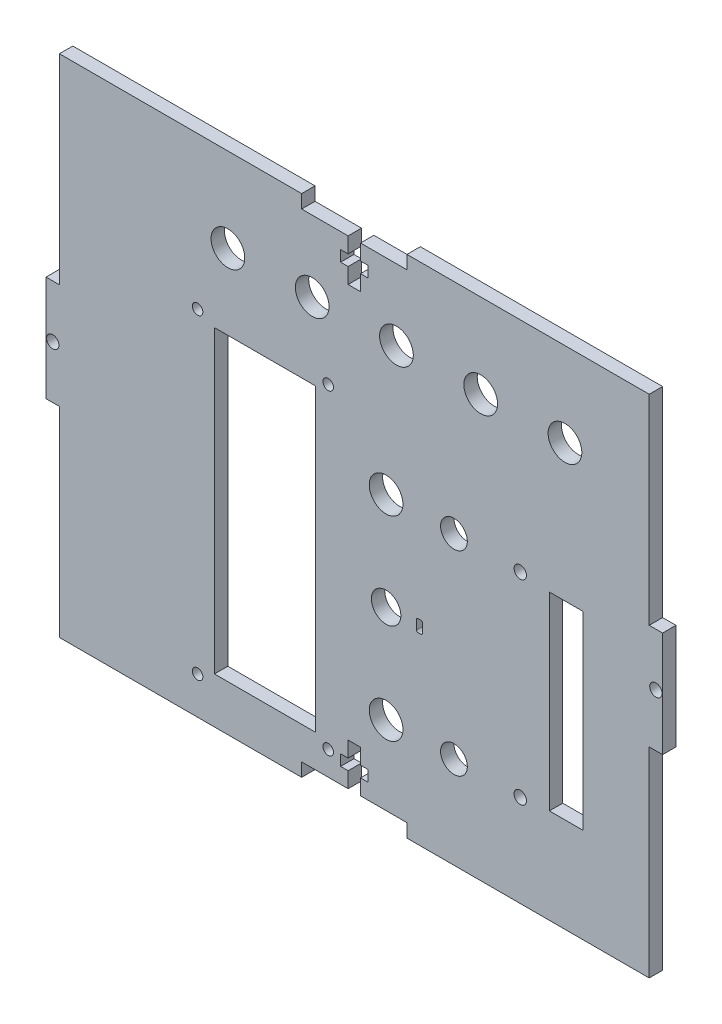
SolidWorks part; units mm, degrees
ref_plane "Front Plane" through (0, 0, 0) normal (0, 0, 1) x (1, 0, 0)
ref_plane "Top Plane" through (0, 0, 0) normal (0, 1, 0) x (1, 0, 0)
ref_plane "Right Plane" through (0, 0, 0) normal (1, 0, 0) x (0, 0, -1)
sketch "Sketch1" plane through (0, 0, 0) normal (0, 0, 1) x (1, 0, 0)
  line L0 (0, 60) -> (0, -60) construction
  line L1 (-70, 60) -> (70, 60)
  line L2 (-70, 60) -> (-70, -60)
  line L3 (-70, -60) -> (70, -60)
  line L4 (70, 60) -> (70, -60)
  line L5 (-70, 60) -> (70, -60) construction
  line L6 (-70, -60) -> (70, 60) construction
  line L7 (-70, 0) -> (70, 0) construction
  line L8 (-3.25, -50.525) -> (3.25, -50.525)
  line L9 (12.5, 60) -> (-12.5, 60)
  line L10 (12.5, 60) -> (12.5, 56.825)
  line L11 (12.5, 56.825) -> (-12.5, 56.825)
  line L12 (-12.5, 60) -> (-12.5, 56.825)
  line L13 (12.5, 60) -> (-12.5, 56.825) construction
  line L14 (12.5, 56.825) -> (-12.5, 60) construction
  line L15 (-1.47, 56.825) -> (1.47, 56.825)
  line L16 (-1.47, 56.825) -> (-1.47, 46.825)
  line L17 (-1.47, 46.825) -> (1.47, 46.825)
  line L18 (1.47, 56.825) -> (1.47, 46.825)
  line L19 (-1.47, 56.825) -> (1.47, 46.825) construction
  line L20 (-1.47, 46.825) -> (1.47, 56.825) construction
  line L21 (-3.25, 53.125) -> (3.25, 53.125)
  line L22 (-3.25, 53.125) -> (-3.25, 50.525)
  line L23 (-3.25, 50.525) -> (3.25, 50.525)
  line L24 (3.25, 53.125) -> (3.25, 50.525)
  line L25 (-3.25, 53.125) -> (3.25, 50.525) construction
  line L26 (-3.25, 50.525) -> (3.25, 53.125) construction
  line L27 (3.25, -53.125) -> (3.25, -50.525)
  line L28 (-3.25, -53.125) -> (3.25, -53.125)
  line L29 (-3.25, -53.125) -> (-3.25, -50.525)
  line L30 (-1.47, -46.825) -> (1.47, -46.825)
  line L31 (1.47, -56.825) -> (1.47, -46.825)
  line L32 (-1.47, -56.825) -> (1.47, -56.825)
  line L33 (-1.47, -56.825) -> (-1.47, -46.825)
  line L34 (12.5, -56.825) -> (-12.5, -56.825)
  line L35 (-12.5, -60) -> (-12.5, -56.825)
  line L36 (12.5, -60) -> (-12.5, -60)
  line L37 (12.5, -60) -> (12.5, -56.825)
  line L38 (73.175, -12.5) -> (70, -12.5)
  line L39 (-73.175, 12.5) -> (-70, 12.5)
  line L40 (-73.175, 12.5) -> (-73.175, -12.5)
  line L41 (-73.175, -12.5) -> (-70, -12.5)
  line L42 (-70, 12.5) -> (-70, -12.5)
  line L43 (-73.175, 12.5) -> (-70, -12.5) construction
  line L44 (-73.175, -12.5) -> (-70, 12.5) construction
  line L45 (70, 12.5) -> (70, -12.5)
  line L46 (73.175, 12.5) -> (70, 12.5)
  line L47 (73.175, 12.5) -> (73.175, -12.5)
  circle A0 centre (-71.5875, 0) radius 1.47
  circle A1 centre (71.5875, 0) radius 1.47
  point P0 (0, 0)
  point P10 (0, 58.4125)
  point P15 (0, 51.825)
  point P20 (0, 51.825)
  point P37 (-71.5875, 0)
  dimension "D11" = 2.94
  dimension "D1" = 120
  dimension "D2" = 140
  dimension "D3" = 3.175
  dimension "D4" = 10
  dimension "D5" = 2.94
  dimension "D6" = 25
  dimension "D7" = 6.5
  dimension "D8" = 2.6
  dimension "D9" = 6.3
  dimension "D10" = 3.175
extrude "Boss-Extrude1" add sketch "Sketch1" along normal mid plane 3.175 contours L21 L24 L23 L18 L17 L16 L22 L11 L12 L1 L2 L3 L4 L10 | L40 L39 L42 L41 | A0 | L38 L45 L46 L47 | A1 region at (0, 0, 0)
sketch "Sketch3" plane through (0, 0, -1.5875) normal (0, 0, -1) x (-1, 0, 0)
  line L0 (-9.6476, 0) -> (-9.6476, -15) construction
  line L5 (-9.6476, -15) -> (-19.2951, -15) construction
  line L6 (-50.3, 7.5) -> (-50.3, -22.5) construction
  line L7 (-46.3, 7.5) -> (-54.3, 7.5)
  line L8 (-46.3, 7.5) -> (-46.3, -37.5)
  line L9 (-46.3, -37.5) -> (-54.3, -37.5)
  line L10 (-54.3, 7.5) -> (-54.3, -37.5)
  line L11 (-48.7125, -40) -> (-48.7125, 10) construction
  line L12 (-51.8875, 10) -> (-51.8875, -40) construction
  line L13 (0, 0) -> (-19.2951, 0) construction
  dimension "D1" = 8
  dimension "D2" = 45
  dimension "D3" = 15
extrude "Cut-Extrude1" cut sketch "Sketch3" against normal through all
sketch "Sketch4" plane through (0, 0, -1.5875) normal (0, 0, -1) x (-1, 0, 0)
  line L0 (33.2, 21.2555) -> (33.2, -48.2445) construction
  line L1 (33.2, 22.1055) -> (9.2, 22.1055)
  line L2 (33.2, 22.1055) -> (33.2, -49.0945)
  line L3 (33.2, -49.0945) -> (9.2, -49.0945)
  line L4 (9.2, 22.1055) -> (9.2, -49.0945)
  line L5 (9.2, -48.2445) -> (9.2, 21.2555) construction
  line L6 (10.05, 22.1055) -> (16.7, 22.1055) construction
  line L7 (32.35, -49.0945) -> (10.05, -49.0945) construction
extrude "Cut-Extrude2" cut sketch "Sketch4" against normal through all
sketch "Sketch5" plane through (0, 0, -1.5875) normal (0, 0, -1) x (-1, 0, 0)
  line L0 (-15.1534, -16.25) -> (-15.7792, -16.25) construction
  line L1 (-15.7792, -13.75) -> (-15.1534, -13.75) construction
  line L2 (-14.9534, -13.95) -> (-14.9534, -16.05) construction
  line L3 (-15.1534, -16.25) -> (-15.7792, -16.25)
  line L4 (-15.7792, -13.75) -> (-15.1534, -13.75)
  line L5 (-14.9534, -13.95) -> (-14.9534, -16.05)
  line L6 (-15.1534, -16.45) -> (-15.7792, -16.45)
  line L7 (-15.7792, -13.55) -> (-15.1534, -13.55)
  line L8 (-14.7534, -13.95) -> (-14.7534, -16.05)
  arc A0 (-15.1534, -16.25) -> (-14.9534, -16.05) centre (-15.1534, -16.05) ccw construction
  arc A1 (-15.9775, -16.0753) -> (-15.7792, -16.25) centre (-15.7792, -16.05) ccw construction
  arc A2 (-15.9775, -13.9247) -> (-15.9775, -16.0753) centre (-7.5458, -15) ccw construction
  arc A3 (-15.7792, -13.75) -> (-15.9775, -13.9247) centre (-15.7792, -13.95) ccw construction
  arc A4 (-14.9534, -13.95) -> (-15.1534, -13.75) centre (-15.1534, -13.95) ccw construction
  arc A5 (-15.1534, -16.25) -> (-14.9534, -16.05) centre (-15.1534, -16.05) ccw
  arc A6 (-15.9775, -16.0753) -> (-15.7792, -16.25) centre (-15.7792, -16.05) ccw
  arc A7 (-15.9775, -13.9247) -> (-15.9775, -16.0753) centre (-7.5458, -15) ccw
  arc A8 (-15.7792, -13.75) -> (-15.9775, -13.9247) centre (-15.7792, -13.95) ccw
  arc A9 (-14.9534, -13.95) -> (-15.1534, -13.75) centre (-15.1534, -13.95) ccw
  arc A10 (-16.1759, -16.1006) -> (-15.7792, -16.45) centre (-15.7792, -16.05) ccw
  arc A11 (-16.1759, -13.8994) -> (-16.1759, -16.1006) centre (-7.5458, -15) ccw
  arc A12 (-15.7792, -13.55) -> (-16.1759, -13.8994) centre (-15.7792, -13.95) ccw
  arc A13 (-14.7534, -13.95) -> (-15.1534, -13.55) centre (-15.1534, -13.95) ccw
  arc A14 (-15.1534, -16.45) -> (-14.7534, -16.05) centre (-15.1534, -16.05) ccw
  dimension "D1" = 0.2
extrude "Cut-Extrude4" cut sketch "Sketch5" against normal through all contours L8 A14 L6 A10 A11 A12 L7 A13
sketch "Sketch6" plane through (0, 0, -1.5875) normal (0, 0, -1) x (-1, 0, 0)
  line L0 (-70, 40) -> (70, 40) construction
  line L1 (-70, 56.825) -> (-70, 12.5) construction
  line L2 (70, 60) -> (70, 12.5) construction
  line L3 (70, 60) -> (12.5, 60) construction
  line L4 (-50, 40) -> (-30, 40)
  line L5 (-30, 40) -> (-10, 40)
  line L6 (-10, 40) -> (10, 40)
  line L7 (10, 40) -> (30, 40)
  line L8 (-70, 60) -> (-70, 12.5) construction
  line L9 (-10, 40) -> (10, 40)
  line L10 (-30, 40) -> (-10, 40)
  line L11 (-50, 40) -> (-30, 40)
  line L12 (-70, 40) -> (-50, 40)
  circle A0 centre (30, 40) radius 4
  circle A1 centre (10, 40) radius 4
  circle A2 centre (-10, 40) radius 4
  circle A3 centre (-30, 40) radius 4
  circle A4 centre (-50, 40) radius 4
  dimension "D4" = 8
  dimension "D1" = 20
  dimension "D2" = 20
  dimension "D3" = 20
  dimension "D5" = 5
extrude "Cut-Extrude5" cut sketch "Sketch6" against normal through all contours A0 | A1 | A2 | A3 | A4
sketch "Sketch9" plane through (0, 0, 1.5875) normal (0, 0, 1) x (1, 0, 0)
  circle A0 centre (-37.2, 23.9055) radius 1.25 construction
  circle A1 centre (-6.2, 23.9055) radius 1.25 construction
  circle A2 centre (-6.2, -51.0945) radius 1.25 construction
  circle A3 centre (-37.2, -51.0945) radius 1.25 construction
  circle A4 centre (-37.2, 23.9055) radius 1.25
  circle A5 centre (-6.2, 23.9055) radius 1.25
  circle A6 centre (-6.2, -51.0945) radius 1.25
  circle A7 centre (-37.2, -51.0945) radius 1.25
  circle A8 centre (39.3875, 8.1613) radius 1.47 construction
  circle A9 centre (39.3875, -38.1613) radius 1.47 construction
  circle A10 centre (39.3875, 8.1613) radius 1.47
  circle A11 centre (39.3875, -38.1613) radius 1.47
extrude "Cut-Extrude6" cut sketch "Sketch9" against normal through all
sketch "Sketch10" plane through (0, 0, -1.5875) normal (0, 0, -1) x (-1, 0, 0)
  line L1 (-23.65, 8.1613) -> (-37.9175, 8.1613) construction
  line L2 (-23.65, -38.1613) -> (-37.9175, -38.1613) construction
  line L3 (-35.65, 19.2863) -> (-35.65, -2.9638) construction
  line L4 (50, 60) -> (50, -60) construction
  line L5 (70, 60) -> (12.5, 60) construction
  line L6 (70, -60) -> (12.5, -60) construction
  line L7 (70, 60) -> (70, 12.5) construction
  line L8 (-35.65, -26.5968) -> (-35.65, -49.7257) construction
  circle A0 centre (-39.3875, 8.1613) radius 1.47 construction
  circle A1 centre (-39.3875, -38.1613) radius 1.47 construction
  point P21 (0, 0)
  point P22 (-35.9175, -26.5968)
  dimension "D1" = 20
  dimension "D2" = 12
sketch "Sketch11" plane through (0, 0, -1.5875) normal (0, 0, -1) x (-1, 0, 0)
  text T0 "Alden Dent PID Box" font "Century Gothic" height 9
  text T1 "Pid On"
sketch "Sketch12" plane through (0, 0, -1.5875) normal (0, 0, -1) x (-1, 0, 0)
  circle A1 centre (-7.5458, -38.1613) radius 4
  circle A2 centre (-7.5458, 8.1613) radius 4
  circle A3 centre (-7.5458, -15) radius 3.5
  arc A6 (-21.105, 10.0596) -> (-21.105, 6.2629) centre (-23.65, 8.1613) ccw construction
  circle A10 centre (-23.65, -38.1613) radius 3.175
  circle A11 centre (-23.65, 8.1613) radius 3.175
  point P18 (0, 0)
  dimension "D1" = 7
  dimension "D2" = 8
  dimension "D3" = 6.35
extrude "Cut-Extrude7" cut sketch "Sketch12" against normal through all
